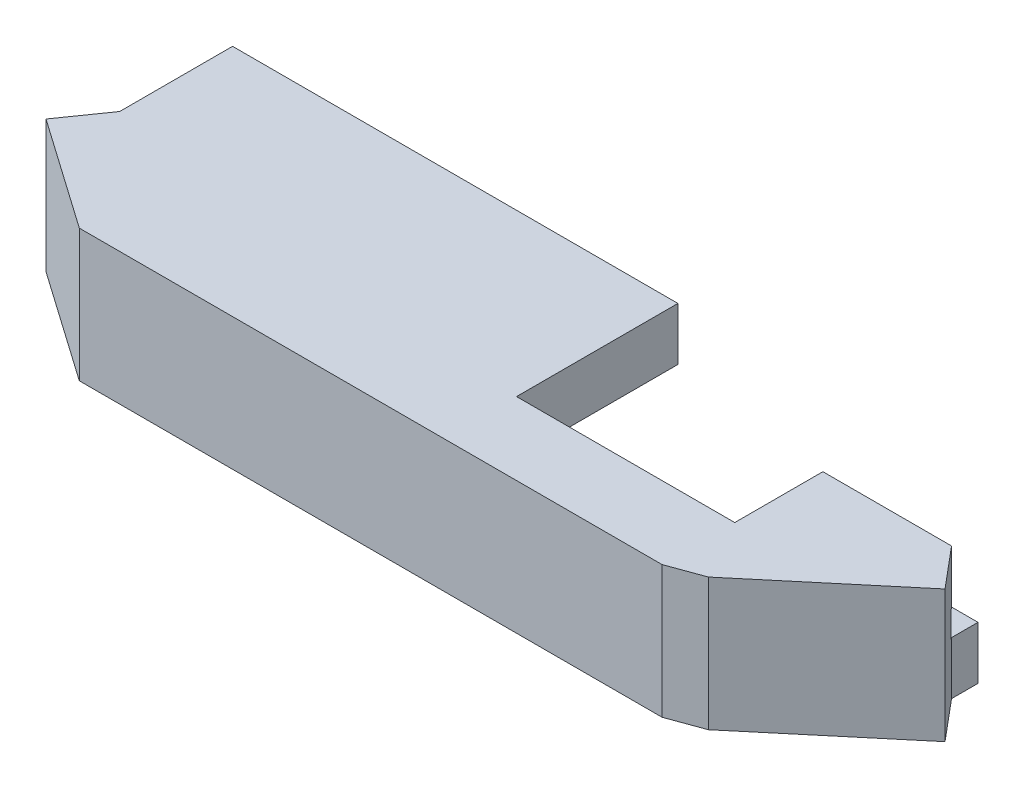
SolidWorks part; units mm, degrees
ref_plane "Front Plane" through (0, 0, 0) normal (0, 0, 1) x (1, 0, 0)
ref_plane "Top Plane" through (0, 0, 0) normal (0, 1, 0) x (1, 0, 0)
ref_plane "Right Plane" through (0, 0, 0) normal (1, 0, 0) x (0, 0, -1)
sketch "Sketch2" plane through (0, 0, 0) normal (0, 1, 0) x (1, 0, 0)
  line L0 (0.1914, 0) -> (8, 0)
  line L1 (0, 0) -> (-7.3724, 5.1622)
  line L2 (18.2588, -0.3) -> (0, -0.3)
  line L5 (18.3, 0) -> (42.8, 0)
  line L6 (8.2412, 0) -> (18.0588, 0)
  line L7 (42.8, -4) -> (0, -4)
  line L9 (18.2588, -0.3) -> (42.8, -0.3)
  line L10 (8.0412, 0) -> (8, 0)
  line L11 (8, 0) -> (8.0884, 0)
  line L12 (42.8, 0) -> (52.5288, 8.1634)
  line L15 (-9.6667, 1.8856) -> (-1.2612, -4)
  line L16 (-7.3724, 5.1622) -> (-7.5444, 4.9164)
  line L17 (-7.3724, 5.1622) -> (-9.6667, 1.8856)
  line L18 (18.2116, 0) -> (18.3, 0)
  line L19 (42.8, -0.3) -> (42.9928, -0.2298)
  line L20 (42.9928, -0.2298) -> (43.6395, 0.3128)
  line L22 (-7.3724, 5.1622) -> (-7.5444, 4.9164)
  line L23 (0, -4) -> (-1.2612, -4)
  line L24 (-7.5444, 4.9164) -> (-0.0946, -0.3)
  line L25 (18.3, 0) -> (27.9042, 0)
  line L26 (43.6395, 0.3128) -> (52.7216, 7.9336)
  line L28 (18.3, 0) -> (26.3, 0)
  line L33 (52.5288, 8.1634) -> (52.7216, 7.9336)
  line L35 (42.8, -4) -> (45.3712, -3.0642)
  line L36 (18.0588, -0.3) -> (18.0588, 0.6076)
  line L37 (13.15, 0) -> (13.15, 4.2)
  line L38 (13.15, 0) -> (13.15, 4.2)
  line L39 (8.2412, -0.3) -> (8.2412, 0.6076)
  line L40 (0.1282, 0) -> (0.58, 0)
  line L42 (0, -0.3) -> (-0.0946, -0.3)
  line L43 (45.3712, -3.0642) -> (55.0999, 5.0992)
  line L44 (0, 0) -> (0.1282, 0)
  line L45 (52.7216, 7.9336) -> (55.0999, 5.0992)
  line L46 (26.3, 1.5) -> (26.3, 13.7)
  line L47 (26.3, 13.7) -> (-7.3724, 13.7)
  line L48 (-7.3724, 5.1622) -> (-7.3724, 13.7)
  line L50 (42.8, 1.5) -> (26.3, 1.5)
  line L51 (42.8, 1.5) -> (42.8, 8.1634)
  line L52 (52.5288, 8.1634) -> (42.8, 8.1634)
  arc A2 (18.2588, -0.3) -> (8.0412, -0.3) centre (13.15, -0.95) ccw
  arc A3 (18.2588, 0) -> (8.0412, 0) centre (13.15, -0.65) ccw
  dimension "D2" = 9
  dimension "D3" = 8
  dimension "D4" = 24.5
  dimension "D5" = 4
  dimension "D6" = 12.7
  dimension "D7" = 140
  dimension "D9" = 10.3
  dimension "D12" = 0.3
  dimension "D13" = 145
  dimension "D14" = 4
  dimension "D15" = 90
  dimension "D16" = 8
  dimension "D18" = 4
  dimension "D20" = 0.3
  dimension "D21" = 13.7
  dimension "D22" = 1.5
extrude "Boss-Extrude1" add sketch "Sketch2" along normal blind 4 contours A3 L18 L5 L25 L12 L52 L51 L50 L46 L47 L48 L1 L44 L40 L0 L10 | L18 A3 L11 A2 | L37 A2 L39 L6 | L36 A2 L37 L6 | L39 L2 L36 L6 | L39 A2 L2 | L2 A2 L36 | A2 L9 L19 L20 L26 L33 L12 L5 L25 L18 | L45 L26 L20 L19 L9 L2 L42 L24 L17 L15 L23 L7 L35 L43 | A2 L11 L10 L0 L40 L44 L1 L16 L24 L42 L2 region at (14.1656, 0, -6.9861) region at (0.3857, 0, 0.1656) region at (13.15, 0, -4.3884) region at (8.1693, 0, -0.0217) region at (18.2794, 0, 0.0355) region at (23.1087, 0, 0.8992) region at (11.0876, 0, -1.7623) region at (18.1307, 0, -0.0217) region at (13.15, 0, 0.15) region at (15.2124, 0, -1.7623)
extrude "Boss-Extrude3" add sketch "Sketch2<4>" against normal blind 2 contours L45 L26 L20 L19 L9 L2 L42 L24 L17 L15 L23 L7 L35 L43 | L36 A2 L37 L6 | L37 A2 L39 L6 | L39 L2 L36 L6 region at (23.1087, 0, 0.8992) region at (11.0876, 0, -1.7623) region at (13.15, 0, 0.15) region at (15.2124, 0, -1.7623)
sketch "Sketch2<4>" plane through (0, 0, 0) normal (0, 1, 0) x (1, 0, 0) same geometry as "Sketch2"
ref_plane "Plane1" through (0, -2, 0) normal (0, -1, 0) x (-1, 0, 0)
sketch "Sketch3" plane through (0, -2, 0) normal (0, -1, 0) x (-1, 0, 0)
  line L0 (-52.5288, 8.1634) -> (-52.5288, 10.1634)
  line L2 (-52.5288, 10.1634) -> (-44.0288, 10.1634)
  line L5 (-44.0288, 10.1634) -> (-44.0288, 1.0311)
  line L6 (-18.2588, 0) -> (-18.2588, 5.1622)
  line L7 (7.3724, 5.1622) -> (-18.2588, 5.1622)
  line L34 (-18.3, 0) -> (-42.8, 0)
  line L41 (-44.0288, 8.1634) -> (-42.8, 8.1634)
  line L49 (-42.8, 1.5) -> (-42.8, 8.1634)
  line L53 (-42.8, 1.5) -> (-26.3, 1.5)
  line L54 (7.3724, 5.1622) -> (7.3724, 13.7)
  line L55 (-26.3, 13.7) -> (7.3724, 13.7)
  line L56 (-26.3, 1.5) -> (-26.3, 13.7)
  line L57 (-52.7216, 7.9336) -> (-55.0999, 5.0992)
  line L58 (0, 0) -> (-0.1282, 0)
  line L59 (-45.3712, -3.0642) -> (-55.0999, 5.0992)
  line L60 (0, -0.3) -> (0.0946, -0.3)
  line L61 (-0.1282, 0) -> (-0.58, 0)
  line L62 (-8.2412, -0.3) -> (-8.2412, 0.6076)
  line L63 (-13.15, 0) -> (-13.15, 4.2)
  line L64 (-13.15, 0) -> (-13.15, 4.2)
  line L65 (-18.0588, -0.3) -> (-18.0588, 0.6076)
  line L66 (-42.8, -4) -> (-45.3712, -3.0642)
  line L67 (-52.5288, 8.1634) -> (-52.7216, 7.9336)
  line L68 (-18.3, 0) -> (-26.3, 0)
  line L69 (-43.6395, 0.3128) -> (-52.7216, 7.9336)
  line L70 (-18.3, 0) -> (-27.9042, 0)
  line L71 (7.5444, 4.9164) -> (0.0946, -0.3)
  line L72 (0, -4) -> (1.2612, -4)
  line L73 (7.3724, 5.1622) -> (7.5444, 4.9164)
  line L74 (-42.9928, -0.2298) -> (-43.6395, 0.3128)
  line L75 (-42.8, -0.3) -> (-42.9928, -0.2298)
  line L76 (-18.2116, 0) -> (-18.3, 0)
  line L77 (7.3724, 5.1622) -> (9.6667, 1.8856)
  line L78 (7.3724, 5.1622) -> (7.5444, 4.9164)
  line L79 (9.6667, 1.8856) -> (1.2612, -4)
  line L80 (-42.8, 0) -> (-52.5288, 8.1634)
  line L81 (-8, 0) -> (-8.0884, 0)
  line L82 (-8.0412, 0) -> (-8, 0)
  line L83 (-18.2588, -0.3) -> (-42.8, -0.3)
  line L84 (-42.8, -4) -> (0, -4)
  line L85 (-8.2412, 0) -> (-18.0588, 0)
  line L86 (-18.2588, -0.3) -> (0, -0.3)
  line L87 (0, 0) -> (7.3724, 5.1622)
  line L88 (-0.1914, 0) -> (-8, 0)
  arc A4 (-18.2588, 0) -> (-8.0412, 0) centre (-13.15, -0.65) cw
  arc A5 (-18.2588, -0.3) -> (-8.0412, -0.3) centre (-13.15, -0.95) cw
  dimension "D1" = 2
  dimension "D2" = 8.5
extrude "Boss-Extrude4" add sketch "Sketch3" along normal blind 4 contours L6 A4 L81 L88 L61 L58 L87 L7 | L80 L5 L2 L0 | L83 A5 L76 L34 L80 L67 L69 L74 L75 | L86 L83 L75 L74 L69 L57 L59 L66 L84 L72 L79 L77 L71 L60 | A5 L63 L85 L62 | A5 L65 L85 L63 | A5 L62 L86 | L65 L86 L62 L85 | L81 A5 L86 L60 L71 L73 L87 L58 L61 L88 | A5 L81 A4 L76 | A5 L86 L65 region at (48.3016, -2, -4.57) region at (47.3711, -2, -6.9995) region at (23.1087, -2, 0.8992) region at (18.1307, -2, -0.0217) region at (13.15, -2, 0.15) region at (18.2352, -2, -0.1116) region at (4.5171, -2, -3.0985) region at (15.2124, -2, -1.7623) region at (8.1693, -2, -0.0217) region at (8.0206, -2, 0.1656) region at (11.0876, -2, -1.7623)
